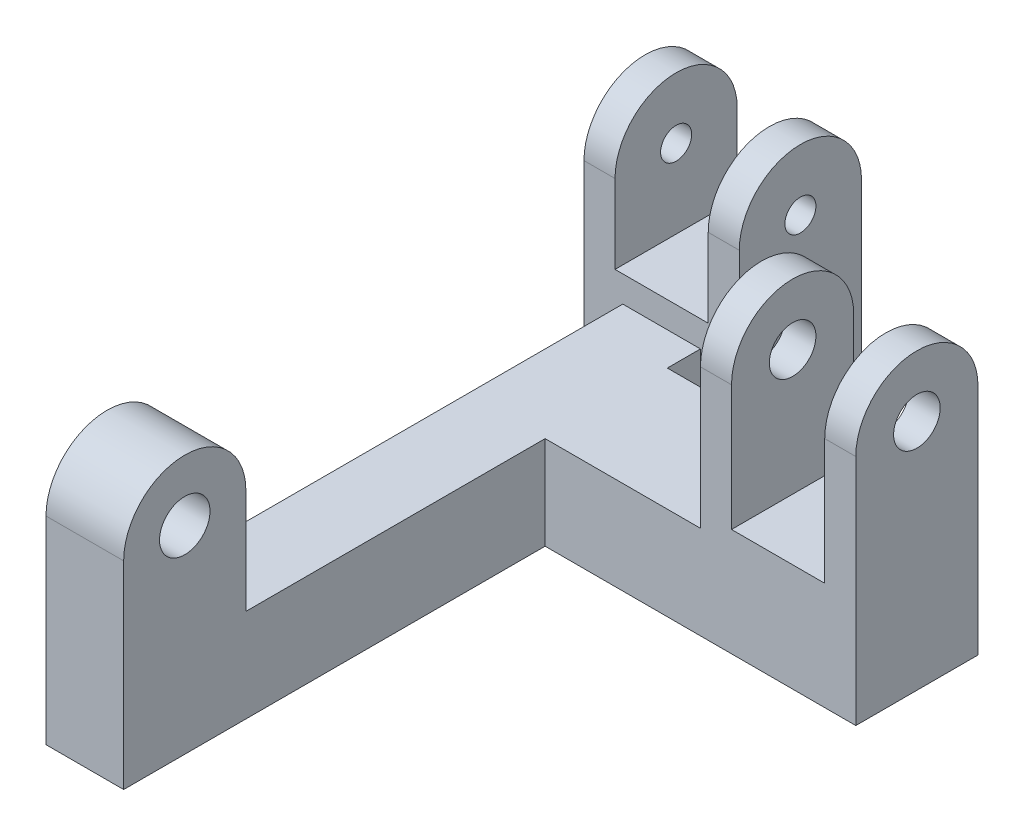
SolidWorks part; units mm, degrees
ref_plane "Front Plane" through (0, 0, 0) normal (0, 0, 1) x (1, 0, 0)
ref_plane "Top Plane" through (0, 0, 0) normal (0, 1, 0) x (1, 0, 0)
ref_plane "Right Plane" through (0, 0, 0) normal (1, 0, 0) x (0, 0, -1)
sketch "Sketch1" plane through (0, 0, 0) normal (1, 0, 0) x (0, 0, -1)
  line L0 (0, 0) -> (0, -12.7577) construction
  line L1 (3.9336, 0) -> (3.9336, -15)
  line L2 (-3.9336, -15) -> (3.9336, -15)
  line L3 (-3.9336, -15) -> (-3.9336, 0)
  circle A0 centre (0, 0) radius 1.5
  arc A1 (3.9336, 0) -> (-3.9336, 0) centre (0, 0) ccw
  dimension "D1" = 3
  dimension "D2" = 15
extrude "Boss-Extrude1" add sketch "Sketch1" along normal mid plane 10
sketch "Sketch2" plane through (0, 0, 0) normal (0, 0, 1) x (1, 0, 0)
  line L0 (5, 3.9336) -> (-5, 3.9336) construction
  line L1 (-3, -8.0664) -> (3, -8.0664)
  line L2 (-3, -8.0664) -> (-3, 3.9336)
  line L3 (-3, 3.9336) -> (3, 3.9336)
  line L4 (3, -8.0664) -> (3, 3.9336)
  line L5 (-3, -8.0664) -> (3, 3.9336) construction
  line L6 (-3, 3.9336) -> (3, -8.0664) construction
  point P0 (0, -2.0664)
  dimension "D1" = 6
  dimension "D2" = 12
extrude "Cut-Extrude1" cut sketch "Sketch2" against normal through all both and the other way through all
sketch "Sketch5" plane through (-5, 0, 0) normal (-1, 0, 0) x (0, 0, 1)
  line L0 (3.9336, 0) -> (3.9336, -15) construction
  line L1 (-3.9336, -15) -> (3.9336, -15)
  line L2 (-3.9336, -15) -> (-3.9336, -9)
  line L3 (-3.9336, -9) -> (3.9336, -9)
  line L4 (3.9336, -15) -> (3.9336, -9)
  dimension "D1" = 6
extrude "Boss-Extrude2" add sketch "Sketch5" along normal blind 10
sketch "Sketch6" plane through (-15, 0, 0) normal (-1, 0, 0) x (0, 0, 1)
  line L1 (23.1992, -9) -> (-6.0664, -9)
  line L2 (31.0664, -6.7577) -> (31.0664, -15)
  line L3 (31.0664, -15) -> (-13.9336, -15)
  line L4 (-13.9336, -6.7577) -> (-13.9336, -15)
  line L5 (3.9336, -9) -> (-3.9336, -9) construction
  line L6 (-3.9336, -15) -> (3.9336, -15) construction
  line L7 (31.0664, -6.7577) -> (31.0664, -2.25)
  line L9 (-13.9336, -6.7577) -> (-13.9336, -2.25)
  line L10 (23.1992, -2.25) -> (23.1992, -9)
  line L11 (-3.9336, -9) -> (-3.9336, -15) construction
  line L12 (0, 0) -> (0, 3.9336) construction
  line L14 (-6.0664, -2.25) -> (-6.0664, -9)
  arc A0 (3.9336, 0) -> (-3.9336, 0) centre (0, 0) ccw construction
  arc A1 (-6.0664, -2.25) -> (-13.9336, -2.25) centre (-10, -2.25) ccw
  arc A2 (31.0664, -2.25) -> (23.1992, -2.25) centre (27.1328, -2.25) ccw
  circle A3 centre (-10, -2.25) radius 1
  circle A4 centre (27.1328, -2.25) radius 1.625
  dimension "D3" = 2
  dimension "D4" = 3.25
  dimension "D1" = 10
  dimension "D2" = 45
  dimension "D5" = 12.75
extrude "Boss-Extrude3" add sketch "Sketch6" along normal blind 5
sketch "Sketch7" plane through (-20, 0, 0) normal (-1, 0, 0) x (0, 0, 1)
  line L0 (-13.9336, -15) -> (-13.9336, -2.25)
  line L1 (-6.0664, -2.25) -> (-6.0664, -15)
  line L2 (31.0664, -15) -> (-13.9336, -15) construction
  line L3 (-6.0664, -15) -> (-13.9336, -15)
  arc A0 (-6.0664, -2.25) -> (-13.9336, -2.25) centre (-10, -2.25) ccw
  circle A1 centre (-10, -2.25) radius 1
  circle A2 centre (-10, -2.25) radius 1 construction
extrude "Boss-Extrude4" add sketch "Sketch7" against normal blind 7.5 and the other way blind 2.5
sketch "Sketch8" plane through (0, 0, -13.9336) normal (0, 0, -1) x (-1, 0, 0)
  line L0 (22.5, 1.6836) -> (12.5, 1.6836) construction
  line L1 (14.5, 1.6836) -> (20.5, 1.6836)
  line L2 (14.5, 1.6836) -> (14.5, -7.3164)
  line L3 (14.5, -7.3164) -> (20.5, -7.3164)
  line L4 (20.5, 1.6836) -> (20.5, -7.3164)
  line L5 (17.5, -15) -> (17.5, 1.6836) construction
  line L6 (22.5, -15) -> (12.5, -15) construction
  point P7 (17.5, 1.6836)
  dimension "D1" = 6
  dimension "D2" = 9
extrude "Cut-Extrude2" cut sketch "Sketch8" against normal up to next and the other way through all
mirror "Mirror2" [suppressed]
delete or keep bodies "Body-Delete/Keep 1" [suppressed] type delete bodies bodies 106
